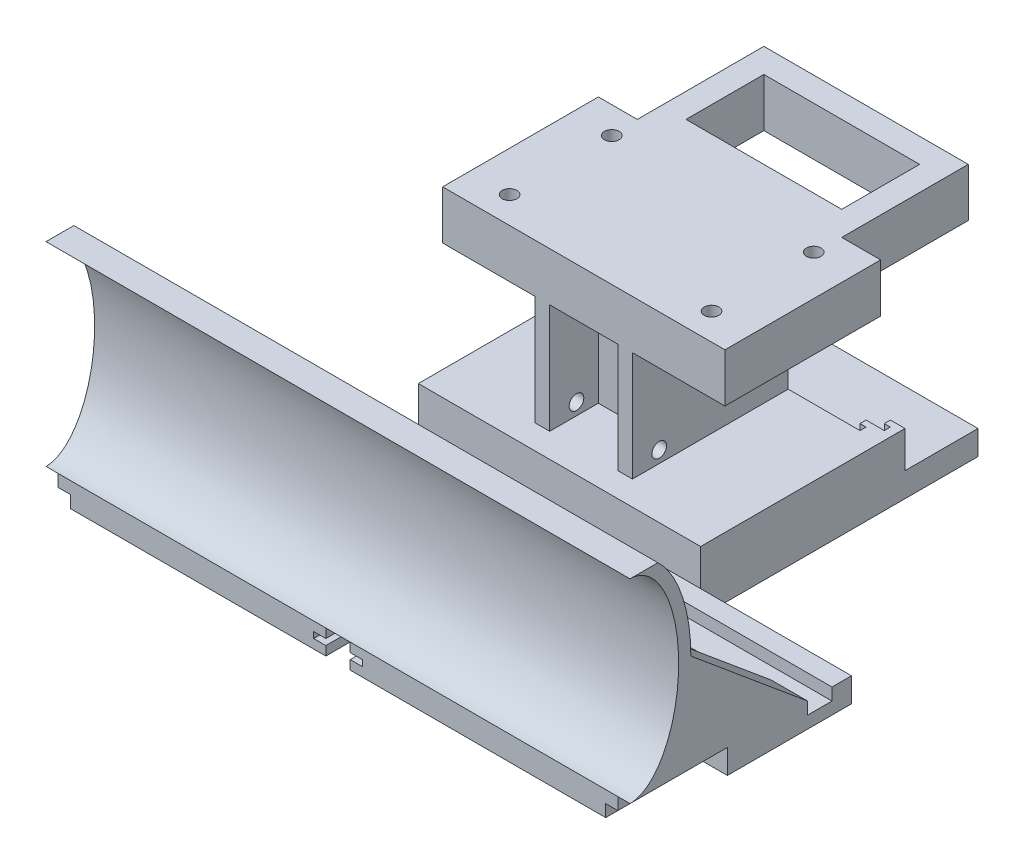
SolidWorks part; units mm, degrees
ref_plane "Alzado" through (0, 0, 0) normal (0, 0, 1) x (1, 0, 0)
ref_plane "Planta" through (0, 0, 0) normal (0, 1, 0) x (1, 0, 0)
ref_plane "Vista lateral" through (0, 0, 0) normal (1, 0, 0) x (0, 0, -1)
sketch "Base-Croquis" plane through (0, 0, 0) normal (0, 1, 0) x (1, 0, 0)
  line L1 (60, -60) -> (-60, -60)
  line L2 (60, -60) -> (60, 60)
  line L3 (60, 60) -> (-60, 60)
  line L4 (-60, -60) -> (-60, 60)
  line L5 (60, -60) -> (-60, 60) construction
  line L6 (60, 60) -> (-60, -60) construction
  point P0 (0, 0)
  dimension "D1" = 120
  dimension "D2" = 120
extrude "Base-Saliente" add sketch "Base-Croquis" along normal blind 5
sketch "Encaje-Ruedas-Croquis" plane through (0, 5, 0) normal (0, 1, 0) x (1, 0, 0)
  line L6 (60, 60) -> (29, 60)
  line L7 (60, 60) -> (60, 3)
  line L8 (60, 3) -> (29, 3)
  line L9 (29, 60) -> (29, 3)
  line L10 (0, -27.5) -> (0, 27.5) construction
  line L11 (-60, 3) -> (-29, 3)
  line L12 (-29, 60) -> (-29, 3)
  line L13 (-60, 60) -> (-29, 60)
  line L14 (-60, 60) -> (-60, 3)
  line L15 (60, 60) -> (60, 65) construction
  line L16 (60, 65) -> (-60, 65) construction
  line L17 (-60, 65) -> (-60, 60) construction
  line L18 (-31, 65) -> (-31, 60) construction
  line L19 (31, 65) -> (31, 60) construction
  dimension "D1" = 31
  dimension "D2" = 57
  dimension "D3" = 5
  dimension "D4" = 29
  dimension "D5" = 29
extrude "Encaje-Ruedas-Cortar" cut sketch "Encaje-Ruedas-Croquis" against normal blind 5
sketch "Caja-Placas-Croquis-1" plane through (0, 5, 0) normal (0, 1, 0) x (1, 0, 0)
  line L0 (29, 40) -> (-29, 40) construction
  line L1 (29, 60) -> (29, 3) construction
  line L2 (-29, 3) -> (-29, 60) construction
  line L3 (29, 60) -> (-29, 60) construction
  line L4 (-29, 8) -> (29, 8) construction
  line L5 (0, 8) -> (0, 40) construction
  line L7 (21, 8) -> (-21, 8)
  line L8 (21, 8) -> (21, 40)
  line L9 (21, 40) -> (-21, 40)
  line L10 (-21, 8) -> (-21, 40)
  line L11 (21, 8) -> (-21, 40) construction
  line L12 (21, 40) -> (-21, 8) construction
  line L13 (-29, 45) -> (29, 45)
  line L14 (-29, 45) -> (-29, 3)
  line L15 (-29, 3) -> (29, 3)
  line L16 (29, 45) -> (29, 3)
  point P12 (0, 24)
  dimension "D1" = 20
  dimension "D2" = 32
  dimension "D3" = 42
  dimension "D4" = 42
  dimension "D5" = 5
extrude "Caja-Placas-Saliente-1" add sketch "Caja-Placas-Croquis-1" along normal blind 5
sketch "Caja-Placas-Croquis-2" plane through (0, 5, 0) normal (0, 1, 0) x (1, 0, 0)
  line L0 (0, 3) -> (0, 45) construction
  line L1 (-29, 3) -> (29, 3) construction
  line L2 (29, 45) -> (-29, 45) construction
  line L4 (21, 8) -> (-21, 8)
  line L5 (21, 8) -> (21, 40)
  line L6 (21, 40) -> (-21, 40)
  line L7 (-21, 8) -> (-21, 40)
  line L8 (21, 8) -> (-21, 40) construction
  line L9 (21, 40) -> (-21, 8) construction
  point P6 (0, 24)
extrude "Caja-Placas-Cortar-2" cut sketch "Caja-Placas-Croquis-2" against normal blind 2.5
sketch "Caja-Placas-Croquis-3" plane through (0, 10, 0) normal (0, 1, 0) x (1, 0, 0)
  line L1 (-29, 45) -> (29, 45)
  line L2 (-29, 45) -> (-29, 3)
  line L3 (-29, 3) -> (29, 3)
  line L4 (29, 45) -> (29, 3)
extrude "Caja-Placas-Saliente-3" add sketch "Caja-Placas-Croquis-3" along normal blind 2.5
sketch "Caja-Placas-Croquis-4" plane through (0, 12.5, 0) normal (0, 1, 0) x (1, 0, 0)
  line L0 (-29, 40) -> (-29, 42.5) construction
  line L1 (-29, 42.5) -> (29, 42.5) construction
  line L2 (29, 45) -> (29, 3) construction
  line L3 (-29, 42.5) -> (-29, 45) construction
  line L4 (-29, 45) -> (29, 45) construction
  line L5 (29, 40) -> (-29, 40) construction
  line L6 (-29, 43.75) -> (29, 43.75) construction
  line L7 (-29, 41.25) -> (29, 41.25) construction
  line L8 (23.5, 42.5) -> (26, 42.5)
  line L9 (-23.5, 40) -> (23.5, 40)
  line L10 (-23.5, 41.25) -> (-23.5, 42.5)
  line L12 (23.5, 41.25) -> (23.5, 42.5)
  line L13 (-26, 45) -> (26, 45)
  line L14 (-26, 45) -> (-26, 43.75)
  line L15 (-26, 42.5) -> (-23.5, 42.5)
  line L16 (26, 45) -> (26, 43.75)
  line L17 (26, 43.75) -> (27.25, 43.75)
  line L19 (26, 42.5) -> (27.25, 42.5)
  line L20 (27.25, 43.75) -> (27.25, 42.5)
  line L21 (23.5, 41.25) -> (24.75, 41.25)
  line L23 (23.5, 40) -> (24.75, 40)
  line L24 (24.75, 41.25) -> (24.75, 40)
  line L25 (-23.5, 40) -> (-24.75, 40)
  line L27 (-23.5, 41.25) -> (-24.75, 41.25)
  line L28 (-24.75, 40) -> (-24.75, 41.25)
  line L29 (-26, 42.5) -> (-27.25, 42.5)
  line L31 (-26, 43.75) -> (-27.25, 43.75)
  line L32 (-27.25, 42.5) -> (-27.25, 43.75)
  dimension "D1" = 47
  dimension "D2" = 5.5
  dimension "D3" = 52
  dimension "D4" = 3
  dimension "D5" = 1.25
  dimension "D6" = 1.25
  dimension "D7" = 1.25
  dimension "D8" = 1.25
extrude "Caja-Placas-Cortar-4" cut sketch "Caja-Placas-Croquis-4" against normal blind 7.5
sketch "Caja-Placas-Croquis-5" plane through (0, 0, 0) normal (0, -1, 0) x (-1, 0, 0)
  line L0 (0, 8) -> (0, 40) construction
  line L1 (15.5, 34.5) -> (-15.5, 34.5)
  line L2 (15.5, 34.5) -> (15.5, 13.5)
  line L3 (15.5, 13.5) -> (-15.5, 13.5)
  line L4 (-15.5, 34.5) -> (-15.5, 13.5)
  line L5 (15.5, 34.5) -> (-15.5, 13.5) construction
  line L6 (15.5, 13.5) -> (-15.5, 34.5) construction
  point P0 (0, 24)
  dimension "D1" = 21
  dimension "D2" = 31
extrude "Caja-Placas-Cortar-5" cut sketch "Caja-Placas-Croquis-5" against normal blind 2.5
sketch "Caja-Motores-Croquis-1" plane through (0, 12.5, 0) normal (0, 1, 0) x (1, 0, 0)
  line L0 (21, 8) -> (-21, 40) construction
  line L1 (-10, 8) -> (10, 8)
  line L2 (-10, 8) -> (-10, 40)
  line L3 (-10, 40) -> (10, 40)
  line L4 (10, 8) -> (10, 40)
  line L5 (-10, 8) -> (10, 40) construction
  line L6 (-10, 40) -> (10, 8) construction
  line L7 (21, 40) -> (-21, 40) construction
  point P0 (0, 24)
  dimension "D1" = 20
extrude "Caja-Motores-Saliente-1" add sketch "Caja-Motores-Croquis-1" along normal blind 22.5
sketch "Agujero-Tornillo-M3-Croquis" plane through (10, 0, 0) normal (1, 0, 0) x (0, 0, -1)
  line L0 (13.5, 35) -> (13.5, 12.5) construction
  line L1 (8, 35) -> (40, 35) construction
  line L2 (3, 12.5) -> (45, 12.5) construction
  line L3 (40, 35) -> (40, 12.5) construction
  circle A0 centre (33.5, 23.7) radius 5
  circle A1 centre (13.5, 32.45) radius 1.5
  circle A2 centre (13.5, 14.95) radius 1.5
  dimension "D1" = 10
  dimension "D2" = 3
  dimension "D3" = 2.55
  dimension "D4" = 2.45
  dimension "D5" = 11.3
  dimension "D6" = 6.5
extrude "Agujero-Tornillo-M3-Cortar" cut sketch "Agujero-Tornillo-M3-Croquis" against normal blind 20
sketch "Caja-Motores-Croquis-2" plane through (0, 35, 0) normal (0, 1, 0) x (1, 0, 0)
  line L1 (-29, 8) -> (29, 8)
  line L2 (-29, 8) -> (-29, 40)
  line L3 (-29, 40) -> (29, 40)
  line L4 (29, 8) -> (29, 40)
  line L5 (-29, 8) -> (29, 40) construction
  line L6 (-29, 40) -> (29, 8) construction
  point P0 (0, 24)
extrude "Caja-Motores-Saliente-2" add sketch "Caja-Motores-Croquis-2" along normal blind 10
sketch "Ajugero-Tuercas-M3-Croquis" plane through (0, 0, -8) normal (0, 0, 1) x (1, 0, 0)
  line L0 (-29, 35) -> (29, 35) construction
  line L1 (-29, 12.5) -> (29, 12.5) construction
  line L2 (-7, 35) -> (7, 35)
  line L3 (-7, 35) -> (-7, 12.5)
  line L4 (-7, 12.5) -> (7, 12.5)
  line L5 (7, 35) -> (7, 12.5)
  line L6 (-10, 35) -> (-10, 12.5) construction
  line L7 (10, 35) -> (10, 12.5) construction
  dimension "D1" = 3
  dimension "D2" = 3
extrude "Ajugero-Tuercas-M3-Cortar" cut sketch "Ajugero-Tuercas-M3-Croquis" against normal blind 10
sketch "Agujer-PCB-Tarugo-Croquis" plane through (0, 45, 0) normal (0, 1, 0) x (1, 0, 0)
  line L0 (0, 8) -> (0, 40) construction
  line L1 (-21, 24) -> (21, 24) construction
  line L2 (-21, 8) -> (-21, 40) construction
  line L3 (21, 8) -> (21, 40) construction
  line L4 (0, 40) -> (0, 8) construction
  line L5 (21, 8) -> (-21, 8) construction
  circle A0 centre (-20.75, 34.5) radius 1.5
  circle A1 centre (20.75, 34.5) radius 1.5
  circle A2 centre (-20.75, 13.5) radius 1.5
  circle A3 centre (20.75, 13.5) radius 1.5
  dimension "D3" = 3
  dimension "D1" = 20.75
  dimension "D2" = 10.5
extrude "Agujer-PCB-Tarugo-Cortar" cut sketch "Agujer-PCB-Tarugo-Croquis" against normal blind 3
sketch "Croquis13" plane through (0, 45, 0) normal (0, 1, 0) x (1, 0, 0)
  line L0 (21, 40) -> (-21, 40) construction
  line L1 (-21, 40) -> (21, 40)
  line L2 (-21, 40) -> (-21, 66)
  line L3 (-21, 66) -> (21, 66)
  line L4 (21, 40) -> (21, 66)
  line L5 (0, 40) -> (0, 66) construction
  line L7 (-16, 45) -> (16, 45)
  line L8 (-16, 45) -> (-16, 61)
  line L9 (-16, 61) -> (16, 61)
  line L10 (16, 45) -> (16, 61)
  line L11 (-16, 45) -> (16, 61) construction
  line L12 (-16, 61) -> (16, 45) construction
  point P6 (0, 40)
  point P10 (0, 53)
  dimension "D1" = 26
  dimension "D2" = 42
  dimension "D3" = 16
  dimension "D4" = 32
extrude "Caja-Bateria-Saliente" add sketch "Croquis13" against normal blind 10
sketch "Caja-Placas-Laterales-Croquis-1" plane through (0, 5, 0) normal (0, 1, 0) x (1, 0, 0)
  line L0 (-60, -1) -> (60, -1) construction
  line L1 (-60, 3) -> (-60, -60) construction
  line L2 (60, -60) -> (60, 3) construction
  line L3 (-60, 3) -> (-29, 3) construction
  line L4 (0, 0) -> (0, -60) construction
  line L5 (-52.5, -1) -> (-11.5, -1)
  line L6 (-52.5, -1) -> (-52.5, -32)
  line L7 (-52.5, -32) -> (-11.5, -32)
  line L8 (-11.5, -1) -> (-11.5, -32)
  line L9 (-60, -60) -> (60, -60) construction
  line L10 (52.5, -32) -> (11.5, -32)
  line L11 (11.5, -1) -> (11.5, -32)
  line L12 (52.5, -1) -> (11.5, -1)
  line L13 (52.5, -1) -> (52.5, -32)
  dimension "D1" = 4
  dimension "D2" = 41
  dimension "D3" = 31
  dimension "D4" = 7.5
extrude "Caja-Placas-Laterales-Cortar-1" cut sketch "Caja-Placas-Laterales-Croquis-1" against normal blind 2.5
sketch "Caja-Placas-Laterales-Croquis-2" plane through (0, 5, 0) normal (0, 1, 0) x (1, 0, 0)
  line L0 (60, -60) -> (60, 3) construction
  line L1 (52.5, -1) -> (60, -1)
  line L2 (52.5, -1) -> (52.5, -6)
  line L3 (52.5, -6) -> (60, -6)
  line L4 (60, -1) -> (60, -6)
  line L5 (0, 0) -> (0, -60) construction
  line L6 (-60, -60) -> (60, -60) construction
  line L7 (-52.5, -6) -> (-60, -6)
  line L8 (-60, -1) -> (-60, -6)
  line L9 (-52.5, -1) -> (-60, -1)
  line L10 (-52.5, -1) -> (-52.5, -6)
  dimension "D1" = 5
extrude "Caja-Placas-Laterales-Cortar-2" cut sketch "Caja-Placas-Laterales-Croquis-2" against normal blind 2.5
sketch "Caja-Placas-Laterales-Croquis-3" plane through (0, 2.5, 0) normal (0, 1, 0) x (1, 0, 0)
  line L0 (11.5, -16.5) -> (52.5, -16.5) construction
  line L1 (11.5, -1) -> (11.5, -32) construction
  line L2 (52.5, -32) -> (52.5, -6) construction
  line L3 (0, 0) -> (0, -60) construction
  line L4 (16.5, -27) -> (47.5, -27)
  line L5 (16.5, -27) -> (16.5, -6)
  line L6 (16.5, -6) -> (47.5, -6)
  line L7 (47.5, -27) -> (47.5, -6)
  line L8 (16.5, -27) -> (47.5, -6) construction
  line L9 (16.5, -6) -> (47.5, -27) construction
  line L10 (-16.5, -6) -> (-47.5, -6)
  line L11 (-47.5, -27) -> (-47.5, -6)
  line L12 (-16.5, -27) -> (-47.5, -27)
  line L13 (-16.5, -27) -> (-16.5, -6)
  point P6 (32, -16.5)
  dimension "D1" = 21
  dimension "D2" = 31
extrude "Caja-Placas-Laterales-Cortar-3" cut sketch "Caja-Placas-Laterales-Croquis-3" against normal blind 2.5
sketch "Parachoques-Croquis-1" plane through (60, 0, 0) normal (1, 0, 0) x (0, 0, -1)
  line L0 (-32, 5) -> (-32, 0) construction
  line L1 (-60, 5) -> (-6, 5) construction
  line L2 (-60, 0) -> (3, 0) construction
  line L3 (3, 0) -> (3, 5) construction
  line L4 (-42.5, 0) -> (-42.5, 5) construction
  line L5 (-42.5, -18.0112) -> (-42.5, 57.6163) construction
  line L6 (-42.5, 45) -> (-30, 45) construction
  line L7 (-42.5, 5) -> (-32, 5) construction
  line L8 (-42.5, 5) -> (-36.7735, 5)
  line L9 (-42.5, 45) -> (-36.7735, 45)
  ellipse E0 centre (-42.5, 25) end of major axis (-42.5, 45) minor radius 10 (-42.5, 5) -> (-42.5, 45) ccw
  ellipse E1 centre (-42.5, 25) end of major axis (-42.5, 2.5) minor radius 12.5 (-36.7735, 5) -> (-36.7735, 45) ccw
  dimension "D1" = 35
  dimension "D2" = 10.5
  dimension "D3" = 20
  dimension "D4" = 10
  dimension "D5" = 12.5
  dimension "D6" = 22.5
extrude "Parachoques-Saliente-1" add sketch "Parachoques-Croquis-1" against normal blind 120
sketch "Parachoques-Croquis-2" plane through (60, 0, 0) normal (1, 0, 0) x (0, 0, -1)
  line L0 (-30, 25) -> (-6, 5)
  line L1 (-6, 5) -> (-36.7735, 5)
  line L2 (-30, 25) -> (-42.5, 25) construction
  line L3 (-42.5, 25) -> (-42.5, 2.5) construction
  ellipse E0 centre (-42.5, 25) end of major axis (-42.5, 2.5) minor radius 12.5 (-36.7735, 5) -> (-36.7735, 45) ccw construction
  ellipse E1 centre (-42.5, 25) end of major axis (-42.5, 2.5) minor radius 12.5 (-30, 25) -> (-36.7735, 5) cw
  dimension "D1" = 22.5
extrude "Parachoques-Saliente-2" add sketch "Parachoques-Croquis-2" against normal blind 7.5
sketch "Parachoques-Croquis-3" plane through (-60, 0, 0) normal (-1, 0, 0) x (0, 0, 1)
  line L0 (6, 5) -> (30, 25)
  line L1 (6, 5) -> (36.7735, 5)
  line L2 (30, 25) -> (42.5, 25) construction
  line L3 (42.5, 25) -> (42.5, 2.5) construction
  ellipse E0 centre (42.5, 25) end of major axis (42.5, 2.5) minor radius 12.5 (30, 25) -> (36.7735, 5) ccw
  dimension "D1" = 22.5
extrude "Parachoques-Saliente-3" add sketch "Parachoques-Croquis-3" against normal blind 7.5
sketch "Parachoques-Croquis-4" plane through (0, 0, 0) normal (1, 0, 0) x (0, 0, -1)
  line L0 (-30, 25) -> (-42.5, 25) construction
  line L1 (-6, 5) -> (-30, 25) construction
  line L2 (-42.5, 25) -> (-42.5, 2.5) construction
  line L3 (-6, 5) -> (-30, 25)
  line L4 (-6, 5) -> (-36.7735, 5)
  ellipse E0 centre (-42.5, 25) end of major axis (-42.5, 2.5) minor radius 12.5 (-30, 25) -> (-36.7735, 45) ccw construction
  ellipse E1 centre (-42.5, 25) end of major axis (-42.5, 2.5) minor radius 12.5 (-30, 25) -> (-36.7735, 5) cw
  dimension "D1" = 22.5
extrude "Parachoques-Saliente-4" add sketch "Parachoques-Croquis-4" against normal blind 5 from vertex starting at point (11.5, 5, 32)
sketch "Parachoques-Croquis-6" plane through (0, 0, 0) normal (1, 0, 0) x (0, 0, -1)
  line L0 (-30, 25) -> (-42.5, 25) construction
  line L2 (-42.5, 25) -> (-42.5, 2.5) construction
  line L3 (-6, 5) -> (-30, 25)
  line L4 (-6, 5) -> (-36.7735, 5)
  ellipse E1 centre (-42.5, 25) end of major axis (-42.5, 2.5) minor radius 12.5 (-30, 25) -> (-36.7735, 5) cw
  dimension "D1" = 22.5
extrude "Parachoques-Saliente-5" add sketch "Parachoques-Croquis-6" along normal blind 3.75 and the other way blind 3.75
extrude "Parachoques-Saliente-6" add sketch "Croquis9<2>" along normal blind 5 from vertex starting at point (-11.5, 5, 32)
sketch "Croquis9<2>" plane through (0, 0, 0) normal (1, 0, 0) x (0, 0, -1) same geometry as "Parachoques-Croquis-6"
sketch "Croquis12" plane through (0, 5, 0) normal (0, 1, 0) x (1, 0, 0)
  line L1 (-60, -42.5) -> (60, -42.5)
  line L2 (-60, -42.5) -> (-60, -60)
  line L3 (-60, -60) -> (60, -60)
  line L4 (60, -42.5) -> (60, -60)
extrude "Encaje-Cuchilla-Cortar-1" cut sketch "Croquis12" against normal blind 5
sketch "Encaje-Cuchilla-Lateral-Croquis-1" plane through (0, 0, 0) normal (0, -1, 0) x (1, 0, 0)
  line L0 (0, 0) -> (0, 42.5) construction
  line L1 (60, 42.5) -> (55, 42.5)
  line L2 (60, 42.5) -> (60, 22.5)
  line L3 (60, 22.5) -> (55, 22.5)
  line L4 (55, 42.5) -> (55, 22.5)
  line L5 (60, 42.5) -> (-60, 42.5) construction
  line L6 (-60, 22.5) -> (-55, 22.5)
  line L7 (-55, 42.5) -> (-55, 22.5)
  line L8 (-60, 42.5) -> (-55, 42.5)
  line L9 (-60, 42.5) -> (-60, 22.5)
  dimension "D1" = 5
  dimension "D2" = 20
extrude "Encaje-Cuchilla-Lateral-Cortar-1" cut sketch "Encaje-Cuchilla-Lateral-Croquis-1" against normal blind 2.5
sketch "Encaje-Cuchilla-Lateral-Croquis-2" plane through (0, 2.5, 0) normal (0, -1, 0) x (1, 0, 0)
  line L0 (55, 22.5) -> (60, 22.5) construction
  line L1 (60, 42.5) -> (57.5, 42.5)
  line L2 (60, 42.5) -> (60, 22.5)
  line L3 (60, 22.5) -> (57.5, 22.5)
  line L4 (57.5, 42.5) -> (57.5, 22.5)
  line L5 (0, 42.5) -> (0, 0) construction
  line L6 (55, 42.5) -> (-55, 42.5) construction
  line L7 (-60, 22.5) -> (-57.5, 22.5)
  line L8 (-57.5, 42.5) -> (-57.5, 22.5)
  line L9 (-60, 42.5) -> (-57.5, 42.5)
  line L10 (-60, 42.5) -> (-60, 22.5)
extrude "Encaje-Cuchilla-Lateral-Cortar-2" cut sketch "Encaje-Cuchilla-Lateral-Croquis-2" against normal blind 2.5
sketch "Encaje-Cuchilla-Lateral-Croquis-3" plane through (57.5, 0, 0) normal (1, 0, 0) x (0, 0, -1)
  line L1 (-22.5, 5) -> (-25, 5)
  line L2 (-22.5, 5) -> (-22.5, 3.75)
  line L3 (-22.5, 3.75) -> (-25, 3.75)
  line L4 (-25, 5) -> (-25, 3.75)
  dimension "D1" = 2.5
  dimension "D2" = 1.25
extrude "Encaje-Cuchilla-Lateral-Cortar-3" cut sketch "Encaje-Cuchilla-Lateral-Croquis-3" against normal blind 1.25
sketch "Encaje-Cuchilla-Lateral-Croquis-4" plane through (55, 0, 0) normal (1, 0, 0) x (0, 0, -1)
  line L0 (-22.5, 5) -> (-22.5, 0) construction
  line L1 (-22.5, 2.5) -> (-25, 2.5)
  line L2 (-22.5, 2.5) -> (-22.5, 1.25)
  line L3 (-22.5, 1.25) -> (-25, 1.25)
  line L4 (-25, 2.5) -> (-25, 1.25)
  dimension "D1" = 2.5
  dimension "D2" = 1.25
extrude "Encaje-Cuchilla-Lateral-Cortar-4" cut sketch "Encaje-Cuchilla-Lateral-Croquis-4" against normal blind 1.25
sketch "Encaje-Cuchilla-Lateral-Croquis-5" plane through (-57.5, 0, 0) normal (-1, 0, 0) x (0, 0, 1)
  line L1 (22.5, 5) -> (25, 5)
  line L2 (22.5, 5) -> (22.5, 3.75)
  line L3 (22.5, 3.75) -> (25, 3.75)
  line L4 (25, 5) -> (25, 3.75)
  dimension "D1" = 1.25
  dimension "D2" = 2.5
extrude "Encaje-Cuchilla-Lateral-Cortar-5" cut sketch "Encaje-Cuchilla-Lateral-Croquis-5" against normal blind 1.25
sketch "Encaje-Cuchilla-Lateral-Croquis-6" plane through (-55, 0, 0) normal (-1, 0, 0) x (0, 0, 1)
  line L0 (22.5, 5) -> (22.5, 0) construction
  line L1 (22.5, 2.5) -> (25, 2.5)
  line L2 (22.5, 2.5) -> (22.5, 1.25)
  line L3 (22.5, 1.25) -> (25, 1.25)
  line L4 (25, 2.5) -> (25, 1.25)
  dimension "D1" = 1.25
  dimension "D2" = 2.5
extrude "Encaje-Cuchilla-Lateral-Cortar-6" cut sketch "Encaje-Cuchilla-Lateral-Croquis-6" against normal blind 1.25
sketch "Encaje-Cuchilla-Central-Croquis" plane through (0, 0, 42.5) normal (0, 0, 1) x (1, 0, 0)
  line L0 (0, 0) -> (0, 5) construction
  line L1 (-29, 5) -> (29, 5) construction
  line L2 (-2.5, 0) -> (2.5, 0)
  line L3 (-2.5, 0) -> (-2.5, 1.875)
  line L4 (-2.5, 5) -> (2.5, 5)
  line L5 (2.5, 0) -> (2.5, 1.875)
  line L6 (-2.5, 0) -> (2.5, 5) construction
  line L7 (-2.5, 5) -> (2.5, 0) construction
  line L8 (-2.5, 3.125) -> (-2.5, 5)
  line L9 (-5, 1.875) -> (-2.5, 1.875)
  line L10 (-5, 1.875) -> (-5, 3.125)
  line L11 (-5, 3.125) -> (-2.5, 3.125)
  line L12 (5, 1.875) -> (5, 3.125)
  line L13 (-5, 1.875) -> (5, 3.125) construction
  line L14 (-5, 3.125) -> (5, 1.875) construction
  line L16 (2.5, 1.875) -> (5, 1.875)
  line L17 (2.5, 3.125) -> (2.5, 5)
  line L18 (2.5, 3.125) -> (5, 3.125)
  point P4 (0, 2.5)
  point P11 (0, 2.5)
  dimension "D1" = 5
  dimension "D2" = 10
  dimension "D3" = 1.25
extrude "Encaje-Cuchilla-Central-Cortar" cut sketch "Encaje-Cuchilla-Central-Croquis" against normal blind 20
